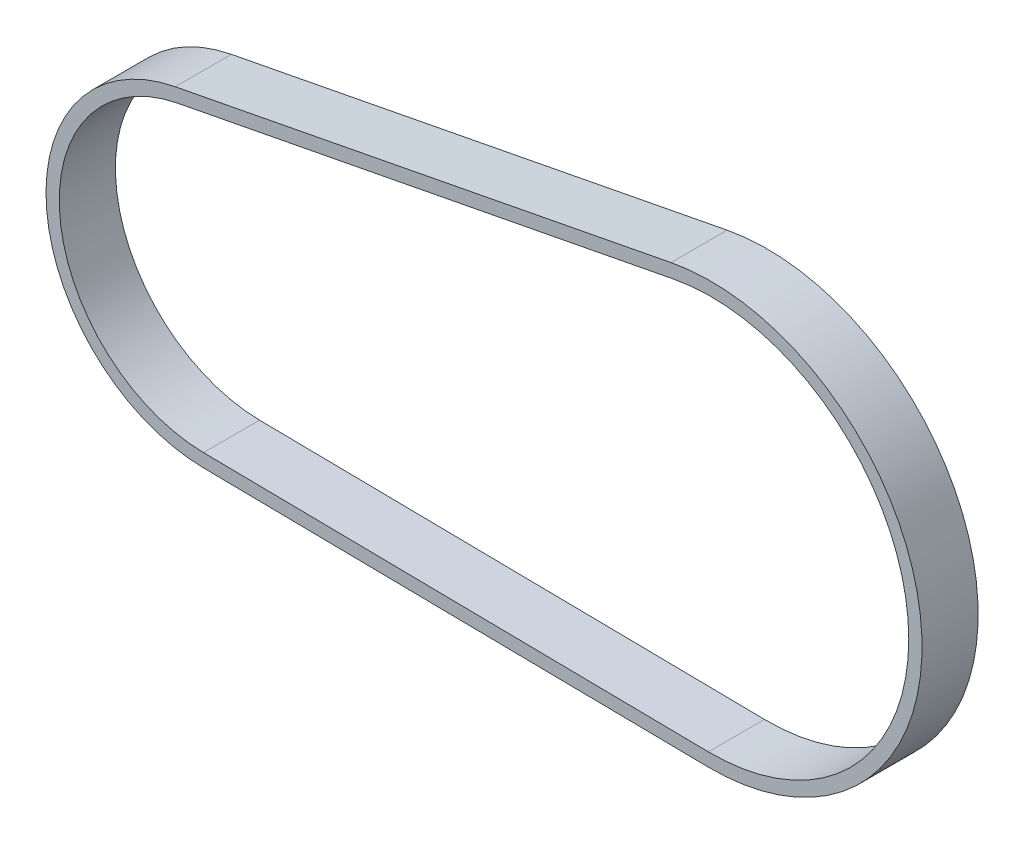
SolidWorks part; units mm, degrees
ref_plane "Front Plane" through (0, 0, 0) normal (0, 0, 1) x (1, 0, 0)
ref_plane "Top Plane" through (0, 0, 0) normal (0, 1, 0) x (1, 0, 0)
ref_plane "Right Plane" through (0, 0, 0) normal (1, 0, 0) x (0, 0, -1)
sketch "Sketch2" plane through (0, 0, 0) normal (0, 0, 1) x (1, 0, 0)
  line L0 (0, 0) -> (1, 0) construction
  line L1 (0, 0) -> (0, 1) construction
  line L4 (56.8682, -18.7939) -> (-0.2404, -18.0324)
  line L5 (-3.4153, 17.7076) -> (52.6649, 28.5239)
  arc A2 (52.6649, 28.5239) -> (56.8682, -18.7939) centre (57.1865, 5.08) cw
  arc A3 (-0.2404, -18.0324) -> (-3.4153, 17.7076) centre (0, 0) cw
extrude "Extrude-Thin1" add sketch "Sketch2" against normal mid plane 6.35 thin thin type one direction reverse wall 1.5
